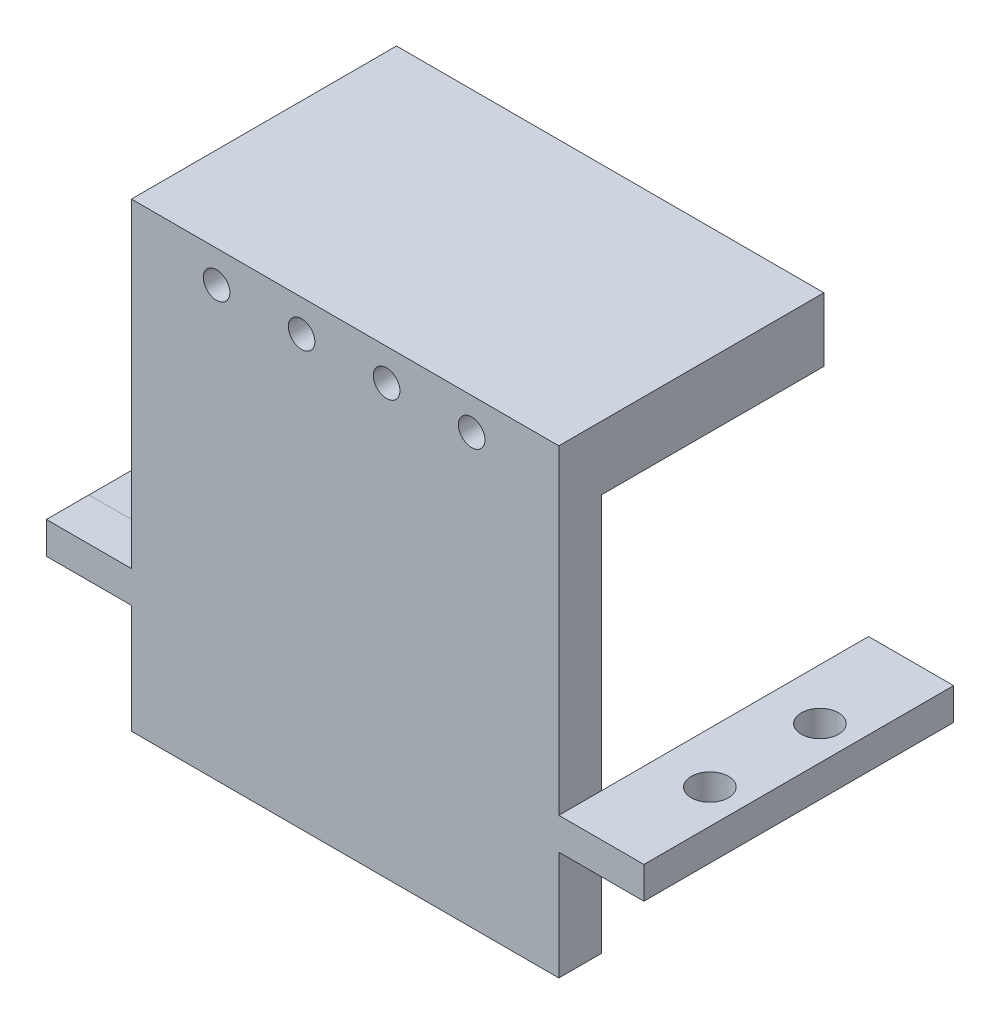
SolidWorks part; units mm, degrees
ref_plane "Front Plane" through (0, 0, 0) normal (0, 0, 1) x (1, 0, 0)
ref_plane "Top Plane" through (0, 0, 0) normal (0, 1, 0) x (1, 0, 0)
ref_plane "Right Plane" through (0, 0, 0) normal (1, 0, 0) x (0, 0, -1)
sketch "Sketch5" plane through (0, 0, 0) normal (0, 0, 1) x (1, 0, 0)
  line L0 (-138.6442, -51.4091) -> (-138.6442, -41.1591)
  line L1 (-138.6442, -41.1591) -> (-146.6442, -41.1591)
  line L2 (-146.6442, -41.1591) -> (-146.6442, -38.1591)
  line L3 (-146.6442, -38.1591) -> (-138.6442, -38.1591)
  line L4 (-138.6442, -38.1591) -> (-138.6442, -14.0591)
  line L5 (-98.4442, -38.1591) -> (-98.4442, -14.0591)
  line L6 (-98.4442, -14.0591) -> (-138.6442, -14.0591)
  line L7 (-98.4442, -38.1591) -> (-90.4442, -38.1591)
  line L8 (-90.4442, -38.1591) -> (-90.4442, -41.1591)
  line L10 (-90.4442, -41.1591) -> (-98.4442, -41.1591)
  line L11 (-98.4442, -41.1591) -> (-98.4442, -51.4091)
  line L12 (-98.4442, -51.4091) -> (-138.6442, -51.4091)
  dimension "D1" = 8
  dimension "D2" = 8
  dimension "D3" = 10.25
  dimension "D5" = 10.25
extrude "Boss-Extrude2" add sketch "Sketch5" along normal blind 4 contours L12 L11 L10 L8 L7 L2 L0 region at (-118.5442, -32.9486, 0)
sketch "Sketch6" plane through (0, 0, 0) normal (0, 0, -1) x (-1, 0, 0)
  line L0 (138.6442, -38.1591) -> (147.6442, -38.1664)
  line L1 (147.6442, -41.1664) -> (138.6442, -41.1664)
  line L2 (147.6442, -41.1664) -> (147.6442, -38.1664)
  line L4 (138.6442, -41.1664) -> (138.6442, -38.1591)
  line M4 (146.6442, -41.1591) -> (146.6442, -38.1591)
  line M22 (138.6442, -41.1591) -> (146.6442, -41.1591)
  line M23 (146.6442, -38.1591) -> (138.6442, -38.1591)
extrude "Boss-Extrude3" add sketch "Sketch6" along normal blind 25.13 contours L4 M22 M4 M23 region at (-142.6428, -39.6607, 0)
sketch "Sketch7" plane through (0, 0, 0) normal (0, 0, -1) x (-1, 0, 0)
  line L1 (90.4442, -41.1591) -> (98.4442, -41.1591)
  line L2 (90.4442, -41.1591) -> (90.4442, -38.1591)
  line L3 (90.4442, -38.1591) -> (98.4442, -38.1591)
  line L4 (98.4442, -41.1591) -> (98.4442, -38.1591)
extrude "Boss-Extrude4" add sketch "Sketch7" along normal blind 25.13
sketch "Sketch32" plane through (0, 0, 0) normal (0, 0, -1) x (-1, 0, 0)
  line L0 (138.6442, -14.0591) -> (98.4442, -14.0591)
  line L1 (138.6442, -14.0591) -> (138.6442, -8.0591)
  line L2 (138.6442, -8.0591) -> (98.4442, -8.0591)
  line L3 (98.4442, -8.0591) -> (98.4442, -14.0591)
extrude "Boss-Extrude6" add sketch "Sketch32" along normal blind 20.93
sketch "Sketch70" plane through (0, -38.1591, 0) normal (0, 1, 0) x (1, 0, 0)
  line L6 (-98.4442, 10.125) -> (-90.4442, 10.125) construction
  line L7 (-90.4442, 10.125) -> (-90.4442, 10.725) construction
  line L8 (-90.4442, 10.725) -> (-90.4442, 9.525) construction
  circle A0 centre (-93.6442, 15.755) radius 1.75
  circle A1 centre (-93.6442, 5.405) radius 1.75
extrude "Cut-Extrude23" cut sketch "Sketch70" against normal blind 5 contours A1 | A0 region at (-93.6442, -38.1591, -15.755) region at (-93.6442, -38.1591, -5.405)
sketch "Sketch71" plane through (0, -41.1591, 0) normal (0, -1, 0) x (-1, 0, 0)
  line L0 (138.6442, 10.125) -> (138.6442, 14.545) construction
  line L2 (93.6442, 15.755) -> (138.6442, 15.755) construction
  line L3 (138.6442, 10.125) -> (145.6442, 10.125) construction
  line L4 (138.6442, 15.755) -> (143.4442, 15.755) construction
  line L5 (143.4442, 15.755) -> (143.4442, 5.405) construction
  circle A0 centre (143.4442, 15.755) radius 1.75
  circle A1 centre (143.4442, 5.405) radius 1.75
extrude "Cut-Extrude24" cut sketch "Sketch71" against normal blind 6 contours A0 | A1 region at (-143.4442, -41.1591, -15.755) region at (-143.4442, -41.1591, -5.405)
sketch "Sketch86" plane through (0, 0, -20.93) normal (0, 0, -1) x (-1, 0, 0)
  circle A0 centre (130.6442, -11.0591) radius 1.25
  circle A1 centre (122.6442, -11.0591) radius 1.25
  circle A2 centre (114.6442, -11.0591) radius 1.25
  circle A3 centre (106.6442, -11.0591) radius 1.25
extrude "Cut-Extrude26" cut sketch "Sketch86" against normal blind 25 and the other way blind 10 contours A2 | A3 | A1
sketch "Sketch88" plane through (0, -14.0591, 0) normal (0, 1, 0) x (1, 0, 0)
  line L1 (-138.6442, 0) -> (-98.4442, 0)
  line L2 (-138.6442, 0) -> (-138.6442, -4)
  line L3 (-138.6442, -4) -> (-98.4442, -4)
  line L4 (-98.4442, 0) -> (-98.4442, -4)
extrude "Boss-Extrude26" add sketch "Sketch88" along normal blind 6
sketch "Sketch89" plane through (0, 0, 4) normal (0, 0, 1) x (1, 0, 0)
  circle A0 centre (-130.6363, -11.0591) radius 1.25
  circle A1 centre (-122.6442, -11.0591) radius 1.25
  circle A2 centre (-114.6442, -11.0591) radius 1.25
  circle A3 centre (-106.6442, -11.0591) radius 1.25
extrude "Cut-Extrude28" cut sketch "Sketch89" against normal blind 30 and the other way blind 4 contours A1 | A2 | A0 | A3 region at (-122.6442, -11.0591, 4) region at (-114.6442, -11.0591, 4)
